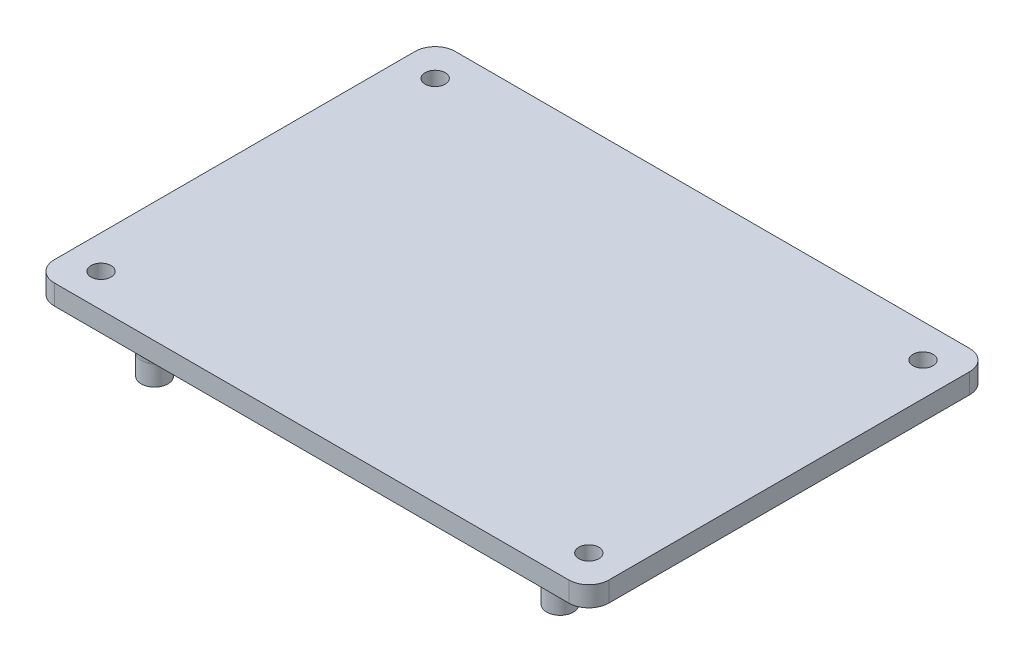
SolidWorks part; units mm, degrees
ref_plane "Front Plane" through (0, 0, 0) normal (0, 0, 1) x (1, 0, 0)
ref_plane "Top Plane" through (0, 0, 0) normal (0, 1, 0) x (1, 0, 0)
ref_plane "Right Plane" through (0, 0, 0) normal (1, 0, 0) x (0, 0, -1)
sketch "Sketch3" plane through (0, 0, 0) normal (0, 1, 0) x (1, 0, 0)
  line L1 (41.5, 30) -> (-41.5, 30)
  line L2 (41.5, 30) -> (41.5, -30)
  line L3 (41.5, -30) -> (-41.5, -30)
  line L4 (-41.5, 30) -> (-41.5, -30)
  line L5 (41.5, 30) -> (-41.5, -30) construction
  line L6 (41.5, -30) -> (-41.5, 30) construction
  point P0 (0, 0)
  dimension "D1" = 60
  dimension "D2" = 83
extrude "Boss-Extrude1" add sketch "Sketch3" along normal blind 3
sketch "Sketch4" plane through (0, 3, 0) normal (0, 1, 0) x (1, 0, 0)
  line L0 (41.5, -30) -> (41.5, 30) construction
  line L4 (-41.5, -30) -> (41.5, -30) construction
  line L5 (41.5, 30) -> (-41.5, 30) construction
  line L8 (-41.5, 30) -> (-41.5, -30) construction
  circle A0 centre (-36.5, 25) radius 1.5
  circle A1 centre (36.5, 25) radius 1.5
  circle A2 centre (36.5, -25) radius 1.5
  circle A3 centre (-36.5, -25) radius 1.5
  point P0 (36.5, 25)
  point P1 (36.5, -25)
  point P2 (-36.5, -25)
  point P3 (-36.5, 25)
  dimension "D1" = 5
  dimension "D2" = 5
  dimension "D3" = 5
  dimension "D4" = 5
  dimension "D5" = 5
  dimension "D6" = 5
  dimension "D7" = 5
  dimension "D8" = 5
extrude "Cut-Extrude1" cut sketch "Sketch4" against normal blind 3
fillet "Fillet2" radius 3 1 edges at (-41.5, 1.5, 30)
fillet "Fillet3" radius 3 3 edges at (-41.5, 1.5, -30) (41.5, 1.5, -30) (41.5, 1.5, 30)
sketch "Sketch7" plane through (0, 3, 0) normal (0, 1, 0) x (1, 0, 0)
  point P0 (-27.8925, -23.5955)
  point P1 (32.1075, -23.5955)
  point P2 (32.1075, 26.4045)
  point P3 (-27.8925, 26.4045)
  dimension "D1" = 60
  dimension "D2" = 60
  dimension "D3" = 50
  dimension "D4" = 50
sketch "Sketch8" plane through (0, 0, 0) normal (0, -1, 0) x (-1, 0, 0)
  circle A1 centre (27.8925, -25.5955) radius 2
  circle A2 centre (-32.0193, -24.8304) radius 2
  circle A3 centre (-32.0193, 24.654) radius 2
  circle A4 centre (27.8925, 24.4045) radius 2
extrude "Boss-Extrude2" add sketch "Sketch8" along normal blind 6
fillet "Fillet4" radius 3 4 edges at (32.0193, 0, -26.654) (32.0193, 0, 22.8304) (-27.8925, 0, -26.4045) (-27.8925, 0, 23.5955)
sketch "Sketch9" plane through (0, -6, 0) normal (0, -1, 0) x (-1, 0, 0)
  circle A0 centre (27.9617, -25.4478) radius 0.3
  circle A2 centre (-32.0193, 24.654) radius 0.3
  circle A3 centre (27.8925, 24.4045) radius 0.3
  circle A4 centre (-32.0193, -24.8304) radius 0.3
extrude "Cut-Extrude2" cut sketch "Sketch9" against normal blind 3
sketch "Sketch10" plane through (0, 3, 0) normal (0, 1, 0) x (1, 0, 0)
  line L0 (0, 5.6012) -> (0, -4.8955)
